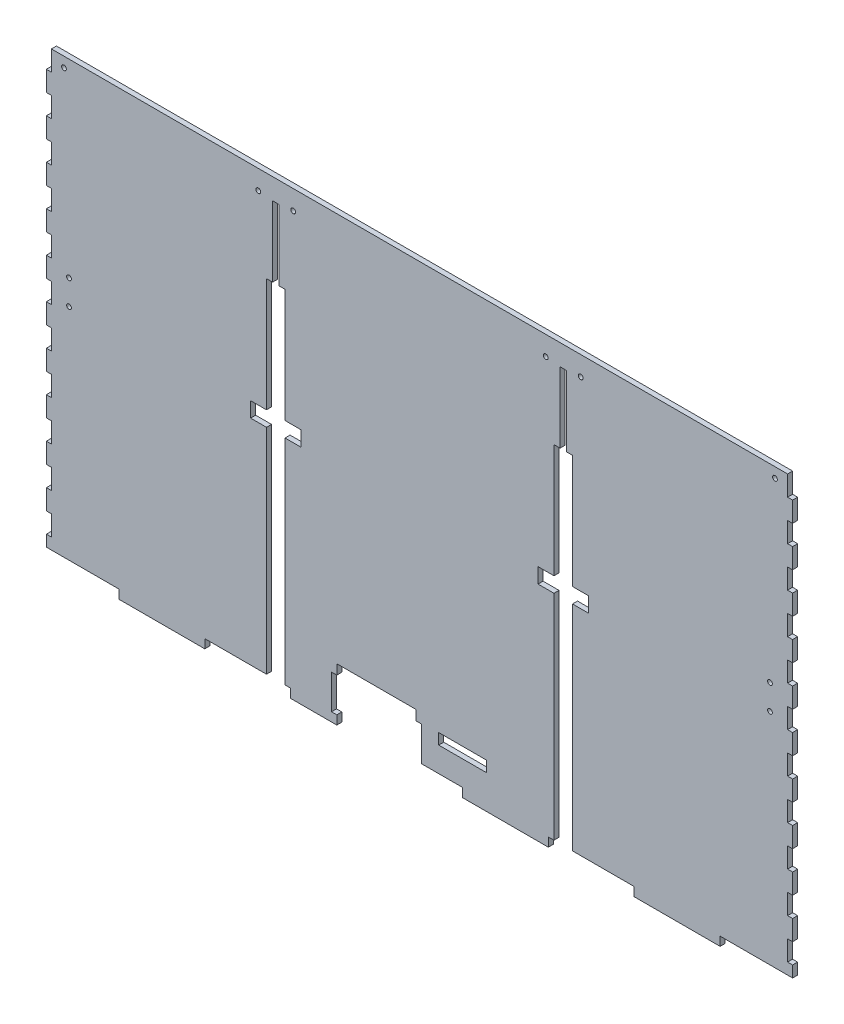
SolidWorks part; units mm, degrees
material "Acrylic (Medium-high impact)"
ref_plane "Front Plane" through (0, 0, 0) normal (0, 0, 1) x (1, 0, 0)
ref_plane "Top Plane" through (0, 0, 0) normal (0, 1, 0) x (1, 0, 0)
ref_plane "Right Plane" through (0, 0, 0) normal (1, 0, 0) x (0, 0, -1)
sketch "Sketch1" plane through (0, 0, 0) normal (0, 0, 1) x (1, 0, 0)
  line L0 (0, 139.7) -> (0, -139.7) construction
  line L1 (-406.4, 139.7) -> (406.4, 139.7)
  line L2 (-406.4, 139.7) -> (-406.4, -139.7)
  line L3 (-406.4, -139.7) -> (406.4, -139.7)
  line L4 (406.4, 139.7) -> (406.4, -139.7)
  line L49 (-381, 127) -> (-381, 114.3)
  line L54 (-381, 139.7) -> (-377.825, 139.7)
  line L55 (-381, 139.7) -> (-381, 127)
  line L56 (-381, 127) -> (-377.825, 127)
  line L57 (-377.825, 139.7) -> (-377.825, 127)
  line L58 (-381, 127) -> (-377.825, 127)
  line L59 (-377.825, 127) -> (-377.825, 114.3)
  line L60 (-381, 114.3) -> (-377.825, 114.3)
  line L61 (-381, 114.3) -> (-381, 101.6)
  line L62 (-381, 114.3) -> (-377.825, 114.3)
  line L63 (-377.825, 114.3) -> (-377.825, 101.6)
  line L64 (-381, 101.6) -> (-377.825, 101.6)
  line L65 (-381, 101.6) -> (-381, 88.9)
  line L66 (-381, 101.6) -> (-377.825, 101.6)
  line L67 (-377.825, 101.6) -> (-377.825, 88.9)
  line L68 (-381, 88.9) -> (-377.825, 88.9)
  line L69 (-381, 88.9) -> (-381, 76.2)
  line L70 (-381, 88.9) -> (-377.825, 88.9)
  line L71 (-377.825, 88.9) -> (-377.825, 76.2)
  line L72 (-381, 76.2) -> (-377.825, 76.2)
  line L73 (-381, 76.2) -> (-381, 63.5)
  line L74 (-381, 76.2) -> (-377.825, 76.2)
  line L75 (-377.825, 76.2) -> (-377.825, 63.5)
  line L76 (-381, 63.5) -> (-377.825, 63.5)
  line L77 (-381, 63.5) -> (-381, 50.8)
  line L78 (-381, 63.5) -> (-377.825, 63.5)
  line L79 (-377.825, 63.5) -> (-377.825, 50.8)
  line L80 (-381, 50.8) -> (-377.825, 50.8)
  line L81 (-381, 50.8) -> (-381, 38.1)
  line L82 (-381, 50.8) -> (-377.825, 50.8)
  line L83 (-377.825, 50.8) -> (-377.825, 38.1)
  line L84 (-381, 38.1) -> (-377.825, 38.1)
  line L85 (-381, 38.1) -> (-381, 25.4)
  line L86 (-381, 38.1) -> (-377.825, 38.1)
  line L87 (-377.825, 38.1) -> (-377.825, 25.4)
  line L88 (-381, 25.4) -> (-377.825, 25.4)
  line L89 (377.825, 127) -> (377.825, 114.3)
  line L90 (377.825, 139.7) -> (381, 139.7)
  line L91 (377.825, 139.7) -> (377.825, 127)
  line L92 (377.825, 127) -> (381, 127)
  line L93 (381, 139.7) -> (381, 127)
  line L94 (377.825, 127) -> (381, 127)
  line L95 (381, 127) -> (381, 114.3)
  line L96 (377.825, 114.3) -> (381, 114.3)
  line L97 (377.825, 114.3) -> (377.825, 101.6)
  line L98 (377.825, 114.3) -> (381, 114.3)
  line L99 (381, 114.3) -> (381, 101.6)
  line L100 (377.825, 101.6) -> (381, 101.6)
  line L101 (377.825, 101.6) -> (377.825, 88.9)
  line L102 (377.825, 101.6) -> (381, 101.6)
  line L103 (381, 101.6) -> (381, 88.9)
  line L104 (377.825, 88.9) -> (381, 88.9)
  line L105 (377.825, 88.9) -> (377.825, 76.2)
  line L106 (377.825, 88.9) -> (381, 88.9)
  line L107 (381, 88.9) -> (381, 76.2)
  line L108 (377.825, 76.2) -> (381, 76.2)
  line L109 (377.825, 76.2) -> (377.825, 63.5)
  line L110 (377.825, 76.2) -> (381, 76.2)
  line L111 (381, 76.2) -> (381, 63.5)
  line L112 (377.825, 63.5) -> (381, 63.5)
  line L113 (377.825, 63.5) -> (377.825, 50.8)
  line L114 (377.825, 63.5) -> (381, 63.5)
  line L115 (381, 63.5) -> (381, 50.8)
  line L116 (377.825, 50.8) -> (381, 50.8)
  line L117 (377.825, 50.8) -> (377.825, 38.1)
  line L118 (377.825, 50.8) -> (381, 50.8)
  line L119 (381, 50.8) -> (381, 38.1)
  line L120 (377.825, 38.1) -> (381, 38.1)
  line L121 (377.825, 38.1) -> (377.825, 25.4)
  line L122 (377.825, 38.1) -> (381, 38.1)
  line L123 (381, 38.1) -> (381, 25.4)
  line L124 (377.825, 25.4) -> (381, 25.4)
  line L125 (-352.2133, -134.112) -> (-352.2133, -139.7)
  line L126 (-406.4, -134.112) -> (-352.2133, -134.112)
  line L127 (-406.4, -134.112) -> (-406.4, -139.7)
  line L128 (-406.4, -139.7) -> (-352.2133, -139.7)
  line L129 (-352.2133, -134.112) -> (-352.2133, -139.7)
  line L130 (-352.2133, -134.112) -> (-298.0267, -134.112)
  line L131 (-298.0267, -134.112) -> (-298.0267, -139.7)
  line L132 (-352.2133, -139.7) -> (-298.0267, -139.7)
  line L133 (-298.0267, -134.112) -> (-298.0267, -139.7)
  line L134 (-298.0267, -134.112) -> (-243.84, -134.112)
  line L135 (-243.84, -134.112) -> (-243.84, -139.7)
  line L136 (-298.0267, -139.7) -> (-243.84, -139.7)
  line L137 (-243.84, -134.112) -> (-243.84, -139.7)
  line L138 (-243.84, -134.112) -> (-189.6533, -134.112)
  line L139 (-189.6533, -134.112) -> (-189.6533, -139.7)
  line L140 (-243.84, -139.7) -> (-189.6533, -139.7)
  line L141 (-189.6533, -134.112) -> (-189.6533, -139.7)
  line L142 (-189.6533, -134.112) -> (-135.4667, -134.112)
  line L143 (-135.4667, -134.112) -> (-135.4667, -139.7)
  line L144 (-189.6533, -139.7) -> (-135.4667, -139.7)
  line L145 (-135.4667, -134.112) -> (-135.4667, -139.7)
  line L146 (-135.4667, -134.112) -> (-81.28, -134.112)
  line L147 (-81.28, -134.112) -> (-81.28, -139.7)
  line L148 (-135.4667, -139.7) -> (-81.28, -139.7)
  line L149 (-81.28, -134.112) -> (-81.28, -139.7)
  line L150 (-81.28, -134.112) -> (-27.0933, -134.112)
  line L151 (-27.0933, -134.112) -> (-27.0933, -139.7)
  line L152 (-81.28, -139.7) -> (-27.0933, -139.7)
  line L153 (-27.0933, -134.112) -> (-27.0933, -139.7)
  line L154 (-27.0933, -134.112) -> (27.0933, -134.112)
  line L155 (27.0933, -134.112) -> (27.0933, -139.7)
  line L156 (-27.0933, -139.7) -> (27.0933, -139.7)
  line L157 (27.0933, -134.112) -> (27.0933, -139.7)
  line L158 (27.0933, -134.112) -> (81.28, -134.112)
  line L159 (81.28, -134.112) -> (81.28, -139.7)
  line L160 (27.0933, -139.7) -> (81.28, -139.7)
  line L161 (81.28, -134.112) -> (81.28, -139.7)
  line L162 (81.28, -134.112) -> (135.4667, -134.112)
  line L163 (135.4667, -134.112) -> (135.4667, -139.7)
  line L164 (81.28, -139.7) -> (135.4667, -139.7)
  line L165 (135.4667, -134.112) -> (135.4667, -139.7)
  line L166 (135.4667, -134.112) -> (189.6533, -134.112)
  line L167 (189.6533, -134.112) -> (189.6533, -139.7)
  line L168 (135.4667, -139.7) -> (189.6533, -139.7)
  line L169 (189.6533, -134.112) -> (189.6533, -139.7)
  line L170 (189.6533, -134.112) -> (243.84, -134.112)
  line L171 (243.84, -134.112) -> (243.84, -139.7)
  line L172 (189.6533, -139.7) -> (243.84, -139.7)
  line L173 (243.84, -134.112) -> (243.84, -139.7)
  line L174 (243.84, -134.112) -> (298.0267, -134.112)
  line L175 (298.0267, -134.112) -> (298.0267, -139.7)
  line L176 (243.84, -139.7) -> (298.0267, -139.7)
  line L177 (298.0267, -134.112) -> (298.0267, -139.7)
  line L178 (298.0267, -134.112) -> (352.2133, -134.112)
  line L179 (352.2133, -134.112) -> (352.2133, -139.7)
  line L180 (298.0267, -139.7) -> (352.2133, -139.7)
  line L181 (352.2133, -134.112) -> (352.2133, -139.7)
  line L182 (352.2133, -134.112) -> (406.4, -134.112)
  line L183 (406.4, -134.112) -> (406.4, -139.7)
  line L184 (352.2133, -139.7) -> (406.4, -139.7)
  line L205 (-90.678, 84.5227) -> (-90.678, -139.7) construction
  line L206 (90.678, 84.5227) -> (90.678, -139.7) construction
  line L207 (-90.678, -27.5886) -> (90.678, -27.5886) construction
  line L208 (-381, 25.4) -> (-381, 12.7)
  line L209 (-381, 25.4) -> (-377.825, 25.4)
  line L210 (-377.825, 25.4) -> (-377.825, 12.7)
  line L211 (-381, 12.7) -> (-377.825, 12.7)
  line L212 (-381, 12.7) -> (-381, 0)
  line L213 (-381, 12.7) -> (-377.825, 12.7)
  line L214 (-377.825, 12.7) -> (-377.825, 0)
  line L215 (-381, 0) -> (-377.825, 0)
  line L224 (-377.825, 0) -> (377.825, 0) construction
  line L229 (377.825, 25.4) -> (377.825, 12.7)
  line L230 (377.825, 25.4) -> (381, 25.4)
  line L231 (381, 25.4) -> (381, 12.7)
  line L232 (377.825, 12.7) -> (381, 12.7)
  line L233 (377.825, 12.7) -> (377.825, 0)
  line L234 (377.825, 12.7) -> (381, 12.7)
  line L235 (381, 12.7) -> (381, 0)
  line L236 (377.825, 0) -> (381, 0)
  line L237 (-381, 0) -> (-381, -12.7)
  line L238 (-381, 0) -> (-377.825, 0)
  line L239 (-377.825, 0) -> (-377.825, -12.7)
  line L240 (-381, -12.7) -> (-377.825, -12.7)
  line L241 (-381, -12.7) -> (-381, -25.4)
  line L242 (-381, -12.7) -> (-377.825, -12.7)
  line L243 (-377.825, -12.7) -> (-377.825, -25.4)
  line L244 (-381, -25.4) -> (-377.825, -25.4)
  line L245 (-381, -25.4) -> (-381, -38.1)
  line L246 (-381, -25.4) -> (-377.825, -25.4)
  line L247 (-377.825, -25.4) -> (-377.825, -38.1)
  line L248 (-381, -38.1) -> (-377.825, -38.1)
  line L249 (-381, -38.1) -> (-381, -50.8)
  line L250 (-381, -38.1) -> (-377.825, -38.1)
  line L251 (-377.825, -38.1) -> (-377.825, -50.8)
  line L252 (-381, -50.8) -> (-377.825, -50.8)
  line L253 (-381, -50.8) -> (-381, -63.5)
  line L254 (-381, -50.8) -> (-377.825, -50.8)
  line L255 (-377.825, -50.8) -> (-377.825, -63.5)
  line L256 (-381, -63.5) -> (-377.825, -63.5)
  line L257 (-381, -63.5) -> (-381, -76.2)
  line L258 (-381, -63.5) -> (-377.825, -63.5)
  line L259 (-377.825, -63.5) -> (-377.825, -76.2)
  line L260 (-381, -76.2) -> (-377.825, -76.2)
  line L261 (-381, -76.2) -> (-381, -88.9)
  line L262 (-381, -76.2) -> (-377.825, -76.2)
  line L263 (-377.825, -76.2) -> (-377.825, -88.9)
  line L264 (-381, -88.9) -> (-377.825, -88.9)
  line L265 (-381, -88.9) -> (-381, -101.6)
  line L266 (-381, -88.9) -> (-377.825, -88.9)
  line L267 (-377.825, -88.9) -> (-377.825, -101.6)
  line L268 (-381, -101.6) -> (-377.825, -101.6)
  line L269 (-381, -101.6) -> (-381, -114.3)
  line L270 (-381, -101.6) -> (-377.825, -101.6)
  line L271 (-377.825, -101.6) -> (-377.825, -114.3)
  line L272 (-381, -114.3) -> (-377.825, -114.3)
  line L273 (-381, -114.3) -> (-381, -127)
  line L274 (-381, -114.3) -> (-377.825, -114.3)
  line L275 (-377.825, -114.3) -> (-377.825, -127)
  line L276 (-381, -127) -> (-377.825, -127)
  line L277 (-381, -127) -> (-381, -139.7)
  line L278 (-381, -127) -> (-377.825, -127)
  line L279 (-377.825, -127) -> (-377.825, -139.7)
  line L280 (-381, -139.7) -> (-377.825, -139.7)
  line L281 (377.825, 0) -> (377.825, -12.7)
  line L282 (377.825, 0) -> (381, 0)
  line L283 (381, 0) -> (381, -12.7)
  line L284 (377.825, -12.7) -> (381, -12.7)
  line L285 (377.825, -12.7) -> (377.825, -25.4)
  line L286 (377.825, -12.7) -> (381, -12.7)
  line L287 (381, -12.7) -> (381, -25.4)
  line L288 (377.825, -25.4) -> (381, -25.4)
  line L289 (377.825, -25.4) -> (377.825, -38.1)
  line L290 (377.825, -25.4) -> (381, -25.4)
  line L291 (381, -25.4) -> (381, -38.1)
  line L292 (377.825, -38.1) -> (381, -38.1)
  line L293 (377.825, -38.1) -> (377.825, -50.8)
  line L294 (377.825, -38.1) -> (381, -38.1)
  line L295 (381, -38.1) -> (381, -50.8)
  line L296 (377.825, -50.8) -> (381, -50.8)
  line L297 (377.825, -50.8) -> (377.825, -63.5)
  line L298 (377.825, -50.8) -> (381, -50.8)
  line L299 (381, -50.8) -> (381, -63.5)
  line L300 (377.825, -63.5) -> (381, -63.5)
  line L301 (377.825, -63.5) -> (377.825, -76.2)
  line L302 (377.825, -63.5) -> (381, -63.5)
  line L303 (381, -63.5) -> (381, -76.2)
  line L304 (377.825, -76.2) -> (381, -76.2)
  line L305 (377.825, -76.2) -> (377.825, -88.9)
  line L306 (377.825, -76.2) -> (381, -76.2)
  line L307 (381, -76.2) -> (381, -88.9)
  line L308 (377.825, -88.9) -> (381, -88.9)
  line L309 (377.825, -88.9) -> (377.825, -101.6)
  line L310 (377.825, -88.9) -> (381, -88.9)
  line L311 (381, -88.9) -> (381, -101.6)
  line L312 (377.825, -101.6) -> (381, -101.6)
  line L313 (377.825, -101.6) -> (377.825, -114.3)
  line L314 (377.825, -101.6) -> (381, -101.6)
  line L315 (381, -101.6) -> (381, -114.3)
  line L316 (377.825, -114.3) -> (381, -114.3)
  line L317 (377.825, -114.3) -> (377.825, -127)
  line L318 (377.825, -114.3) -> (381, -114.3)
  line L319 (381, -114.3) -> (381, -127)
  line L320 (377.825, -127) -> (381, -127)
  line L321 (377.825, -127) -> (377.825, -139.7)
  line L322 (377.825, -127) -> (381, -127)
  line L323 (381, -127) -> (381, -139.7)
  line L324 (377.825, -139.7) -> (381, -139.7)
  point P6 (0, 0)
  point P128 (0, -27.5886)
  point P153 (0, 0)
  dimension "D4" = 12.7
  dimension "D5" = 3.175
  dimension "D10" = 181.356
  dimension "D12" = 755.65
  dimension "D8" = 812.8
  dimension "D11" = 54.1867
  dimension "D2" = 273.812
  dimension "D9" = 279.4
  dimension "D3" = 22
  dimension "D7" = 15
extrude "Main Extrude" add sketch "Sketch1" along normal blind 3.175 contours L321 L317 L313 L309 L305 L301 L297 L293 L289 L285 L281 L233 L229 L121 L117 L113 L109 L105 L101 L97 L89 L91 L1 L57 L59 L63 L67 L71 L75 L79 L83 L87 L210 L214 L239 L243 L247 L251 L255 L259 L263 L267 L271 L275 L279 L126 L130 L134 L138 L142 L146 | L277 L273 L269 L265 L261 L257 L253 L249 L245 L241 L237 L212 L208 L85 L81 L77 L73 L69 L65 L61 L49 L55 L1 L2 L126 | L319 L323 L182 L4 L1 L93 L95 L99 L103 L107 L111 L115 L119 L123 L231 L235 L283 L287 L291 L295 L299 L303 L307 L311 L315 | L126 L279 L3 L125 | L135 L134 L131 L3 | L143 L142 L139 L3 | L151 L150 L147 L3 | L159 L158 L155 L3 | L167 L166 L163 L3 | L175 L174 L171 L3 | L323 L182 L321 L184 | L89 L96 L95 L92 | L101 L104 L103 L100 | L109 L112 L111 L108 | L117 L120 L119 L116 | L229 L232 L231 L124 | L281 L284 L283 L236 | L289 L292 L291 L288 | L297 L300 L299 L296 | L305 L308 L307 L304 | L313 L316 L315 L312 | L323 L320 L321 L182 | L49 L60 L59 L56 | L65 L68 L67 L64 | L73 L76 L75 L72 | L81 L84 L83 L80 | L208 L211 L210 L88 | L237 L240 L239 L215 | L245 L248 L247 L244 | L253 L256 L255 L252 | L261 L264 L263 L260 | L269 L272 L271 L268 | L279 L276 L277 L126 | L277 L126 L2 L3 | L321 L182 L179 L3 | L182 L323 L3 L4 | L279 L126 L277 L128 region at (-393.7, 2.794, 0) region at (-393.7, -136.906, 0) region at (0, 2.794, 0) region at (-379.4125, 120.65, 0) region at (-379.4125, -130.556, 0) region at (-379.4125, -136.906, 0) region at (-365.0192, -136.906, 0) region at (393.7, 2.794, 0) region at (379.4125, 120.65, 0) region at (-379.4125, 95.25, 0) region at (-379.4125, -107.95, 0) region at (-270.9333, -136.906, 0) region at (393.7, -136.906, 0) region at (379.4125, 95.25, 0) region at (-379.4125, 69.85, 0) region at (-379.4125, -82.55, 0) region at (379.4125, -136.906, 0) region at (379.4125, -130.556, 0) region at (-162.56, -136.906, 0) region at (365.0192, -136.906, 0) region at (379.4125, 69.85, 0) region at (-379.4125, 44.45, 0) region at (-379.4125, -57.15, 0) region at (379.4125, -107.95, 0) region at (-54.1867, -136.906, 0) region at (270.9333, -136.906, 0) region at (379.4125, 44.45, 0) region at (-379.4125, 19.05, 0) region at (-379.4125, -31.75, 0) region at (379.4125, -82.55, 0) region at (54.1867, -136.906, 0) region at (162.56, -136.906, 0) region at (379.4125, 19.05, 0) region at (-379.4125, -6.35, 0) region at (379.4125, -57.15, 0) region at (379.4125, -6.35, 0) region at (379.4125, -31.75, 0)
sketch "Sketch8" plane through (0, 0, 3.175) normal (0, 0, 1) x (1, 0, 0)
  line L0 (-406.4, 139.7) -> (-406.4, -139.7) construction
  line L1 (-381, 28.2575) -> (-384.175, 28.2575)
  line L2 (-381, 28.2575) -> (-381, -3.6195)
  line L3 (-381, -3.6195) -> (-384.175, -3.6195)
  line L4 (-384.175, 28.2575) -> (-384.175, -3.6195)
  line L5 (-406.4, -139.7) -> (-352.2133, -139.7) construction
  line L6 (381, 28.2575) -> (384.175, 28.2575)
  line L7 (381, 28.2575) -> (381, -3.6195)
  line L8 (381, -3.6195) -> (384.175, -3.6195)
  line L9 (384.175, 28.2575) -> (384.175, -3.6195)
  line L11 (-381, 88.9) -> (-381, 76.2) construction
  line L12 (-352.2133, -134.112) -> (-298.0267, -134.112) construction
  line L13 (381, 88.9) -> (381, 76.2) construction
  line L14 (-393.7, -120.65) -> (393.7, -120.65) construction
  circle A0 centre (-393.7, -120.65) radius 1.5
  circle A1 centre (393.7, -120.65) radius 1.5
  point P6 (0, -120.65)
  point P16 (-384.175, 12.319)
  dimension "D5" = 3
  dimension "D1" = 31.877
  dimension "D2" = 3.175
  dimension "D3" = 146.431
  dimension "D4" = 19.05
  dimension "D6" = 12.7
extrude "Mount Holes" cut sketch "Sketch8" against normal through all
sketch "Sketch3" plane through (0, 0, 3.175) normal (0, 0, 1) x (1, 0, 0)
  line L0 (-135.4667, -134.112) -> (-81.28, -134.112) construction
  line L1 (-96.52, 126.492) -> (-84.836, 126.492)
  line L2 (-96.52, 126.492) -> (-96.52, -134.112)
  line L3 (-96.52, -134.112) -> (-84.836, -134.112)
  line L4 (-84.836, 126.492) -> (-84.836, -134.112)
  line L5 (81.28, -134.112) -> (135.4667, -134.112) construction
  line L6 (84.836, 126.492) -> (96.52, 126.492)
  line L7 (84.836, 126.492) -> (84.836, -134.112)
  line L8 (84.836, -134.112) -> (96.52, -134.112)
  line L9 (96.52, 126.492) -> (96.52, -134.112)
  line L10 (-84.836, -3.81) -> (84.836, -3.81) construction
  line L12 (-106.553, 10.3505) -> (-74.803, 10.3505)
  line L13 (-106.553, 10.3505) -> (-106.553, 0.8255)
  line L14 (-106.553, 0.8255) -> (-74.803, 0.8255)
  line L15 (-74.803, 10.3505) -> (-74.803, 0.8255)
  line L16 (74.803, 10.3505) -> (106.553, 10.3505)
  line L17 (74.803, 10.3505) -> (74.803, 0.8255)
  line L18 (74.803, 0.8255) -> (106.553, 0.8255)
  line L19 (106.553, 10.3505) -> (106.553, 0.8255)
  line L20 (-96.52, 126.492) -> (-92.6465, 126.492)
  line L21 (-96.52, 126.492) -> (-96.52, 82.042)
  line L22 (-96.52, 82.042) -> (-92.6465, 82.042)
  line L23 (-92.6465, 126.492) -> (-92.6465, 82.042)
  line L24 (-84.836, 126.492) -> (-88.7095, 126.492)
  line L25 (-84.836, 126.492) -> (-84.836, 82.042)
  line L26 (-84.836, 82.042) -> (-88.7095, 82.042)
  line L27 (-88.7095, 126.492) -> (-88.7095, 82.042)
  line L28 (84.836, 126.492) -> (88.7095, 126.492)
  line L29 (84.836, 126.492) -> (84.836, 82.042)
  line L30 (84.836, 82.042) -> (88.7095, 82.042)
  line L31 (88.7095, 126.492) -> (88.7095, 82.042)
  line L32 (96.52, 126.492) -> (92.6465, 126.492)
  line L33 (96.52, 126.492) -> (96.52, 82.042)
  line L34 (96.52, 82.042) -> (92.6465, 82.042)
  line L35 (92.6465, 126.492) -> (92.6465, 82.042)
  point P14 (-90.678, 126.492)
  point P15 (90.678, 126.492)
  point P16 (0, -3.81)
  point P27 (-90.678, 10.3505)
  point P28 (90.678, 10.3505)
  point P29 (-74.803, 5.588)
  dimension "D1" = 11.684
  dimension "D2" = 260.604
  dimension "D3" = 181.356
  dimension "D4" = 9.525
  dimension "D5" = 139.7
  dimension "D6" = 31.75
  dimension "D8" = 3.937
  dimension "D7" = 44.45
extrude "Door Slots" cut sketch "Sketch3" against normal through all contours L2 L12 L4 L1 | L2 L14 L4 L12 | L15 L12 L4 L14 | L13 L14 L2 L12 | L14 L2 L3 L4 | L7 L16 L9 L6 | L7 L18 L9 L16 | L19 L16 L9 L18 | L17 L18 L7 L16 | L18 L7 L8 L9 region at (-90.678, 56.2317, 3.175) region at (-90.678, 5.588, 3.175) region at (-101.5365, 5.588, 3.175) region at (-90.678, -66.6433, 3.175) region at (-79.8195, 5.588, 3.175) region at (90.678, 56.2317, 3.175) region at (90.678, 5.588, 3.175) region at (79.8195, 5.588, 3.175) region at (90.678, -66.6432, 3.175) region at (101.5365, 5.588, 3.175)
sketch "Sketch4" plane through (0, 0, 0) normal (0, 0, 1) x (1, 0, 0)
  line L1 (-81.28, -139.7) -> (-27.0933, -139.7) construction
  line L2 (-55.48, -112.41) -> (-52.178, -112.41)
  line L3 (-52.178, -112.41) -> (-52.178, -106.172)
  line L4 (-52.178, -106.172) -> (-2.178, -106.172)
  line L5 (-2.178, -106.172) -> (-2.178, -112.41)
  line L6 (-2.178, -112.41) -> (1.124, -112.41)
  line L9 (-55.48, -112.41) -> (-55.48, -134.112)
  line L10 (-55.48, -134.112) -> (-52.178, -134.112)
  line L11 (-52.178, -134.112) -> (-52.178, -139.7)
  line L12 (1.124, -112.41) -> (1.124, -134.112)
  line L13 (1.124, -134.112) -> (-2.178, -134.112)
  line L14 (-2.178, -134.112) -> (-2.178, -139.7)
  line L15 (-52.178, -139.7) -> (-2.178, -139.7)
  line L16 (-27.0933, -134.112) -> (27.0933, -134.112) construction
  line L18 (12.128, -111.633) -> (42.228, -111.633)
  line L19 (12.128, -111.633) -> (12.128, -118.491)
  line L20 (12.128, -118.491) -> (42.228, -118.491)
  line L21 (42.228, -111.633) -> (42.228, -118.491)
  line L22 (-27.0933, -134.112) -> (27.0933, -134.112) construction
  line L24 (-96.52, -134.112) -> (-84.836, -134.112) construction
  line L25 (84.836, -134.112) -> (96.52, -134.112) construction
  point P9 (-27.178, -106.172)
  point P10 (-27.178, -139.7)
  point P22 (27.178, -118.491)
  point P25 (90.678, -134.112)
  point P30 (-90.678, -134.112)
  dimension "D1" = 50
  dimension "D2" = 3.302
  dimension "D4" = 21.702
  dimension "D5" = 30.1
  dimension "D9" = 63.5
  dimension "D8" = 63.5
  dimension "D7" = 15.621
extrude "Trough and Lever Holes" cut sketch "Sketch4" along normal through all contours L11 L15 L14 L13 L12 L6 L5 L4 L3 L2 L9 L10 | L21 L18 L19 L20 region at (-27.178, -122.9616, 0) region at (27.178, -115.062, 0)
sketch "Sketch5" plane through (0, 0, 3.175) normal (0, 0, 1) x (1, 0, 0)
  line L0 (-90.678, 126.492) -> (-90.678, -134.112) construction
  line L1 (-96.52, 126.492) -> (-84.836, 126.492) construction
  line L2 (-96.52, -134.112) -> (-84.836, -134.112) construction
  line L3 (90.678, 126.492) -> (90.678, -134.112) construction
  line L4 (84.836, 126.492) -> (96.52, 126.492) construction
  line L5 (84.836, -134.112) -> (96.52, -134.112) construction
  line L6 (-135.4667, -134.112) -> (-96.52, -134.112) construction
  line L19 (-99.51, -134.112) -> (-95.8319, -134.112)
  line L20 (-99.51, -134.112) -> (-99.51, -108.712)
  line L21 (-99.51, -108.712) -> (-95.8319, -108.712)
  line L22 (-95.8319, -134.112) -> (-95.8319, -108.712)
  line L24 (-99.51, -108.712) -> (-95.8319, -108.712)
  line L25 (-99.51, -108.712) -> (-99.51, -83.312)
  line L26 (-99.51, -83.312) -> (-95.8319, -83.312)
  line L27 (-95.8319, -108.712) -> (-95.8319, -83.312)
  line L28 (-95.8319, -83.312) -> (-99.51, -83.312)
  line L29 (-95.8319, -83.312) -> (-95.8319, -57.912)
  line L30 (-95.8319, -57.912) -> (-99.51, -57.912)
  line L31 (-99.51, -83.312) -> (-99.51, -57.912)
  line L32 (-99.51, -57.912) -> (-95.8319, -57.912)
  line L33 (-99.51, -57.912) -> (-99.51, -32.512)
  line L34 (-99.51, -32.512) -> (-95.8319, -32.512)
  line L35 (-95.8319, -57.912) -> (-95.8319, -32.512)
  line L36 (-95.8319, -32.512) -> (-99.51, -32.512)
  line L37 (-95.8319, -32.512) -> (-95.8319, -7.112)
  line L38 (-95.8319, -7.112) -> (-99.51, -7.112)
  line L39 (-99.51, -32.512) -> (-99.51, -7.112)
  line L40 (-81.846, -108.712) -> (-85.5241, -108.712)
  line L41 (-85.5241, -134.112) -> (-85.5241, -108.712)
  line L42 (-81.846, -134.112) -> (-85.5241, -134.112)
  line L43 (-81.846, -134.112) -> (-81.846, -108.712)
  line L44 (-81.846, -83.312) -> (-85.5241, -83.312)
  line L45 (-85.5241, -108.712) -> (-85.5241, -83.312)
  line L46 (-81.846, -108.712) -> (-85.5241, -108.712)
  line L47 (-81.846, -108.712) -> (-81.846, -83.312)
  line L48 (-85.5241, -57.912) -> (-81.846, -57.912)
  line L49 (-81.846, -83.312) -> (-81.846, -57.912)
  line L50 (-85.5241, -83.312) -> (-81.846, -83.312)
  line L51 (-85.5241, -83.312) -> (-85.5241, -57.912)
  line L52 (-81.846, -32.512) -> (-85.5241, -32.512)
  line L53 (-85.5241, -57.912) -> (-85.5241, -32.512)
  line L54 (-81.846, -57.912) -> (-85.5241, -57.912)
  line L55 (-81.846, -57.912) -> (-81.846, -32.512)
  line L56 (-85.5241, -7.112) -> (-81.846, -7.112)
  line L57 (-81.846, -32.512) -> (-81.846, -7.112)
  line L58 (-85.5241, -32.512) -> (-81.846, -32.512)
  line L59 (-85.5241, -32.512) -> (-85.5241, -7.112)
  line L60 (0, -1.7463) -> (0, 1.7463) construction
  line L61 (99.51, -108.712) -> (95.8319, -108.712)
  line L62 (95.8319, -134.112) -> (95.8319, -108.712)
  line L63 (99.51, -134.112) -> (95.8319, -134.112)
  line L64 (99.51, -134.112) -> (99.51, -108.712)
  line L65 (99.51, -83.312) -> (95.8319, -83.312)
  line L66 (95.8319, -108.712) -> (95.8319, -83.312)
  line L67 (99.51, -108.712) -> (95.8319, -108.712)
  line L68 (99.51, -108.712) -> (99.51, -83.312)
  line L69 (95.8319, -57.912) -> (99.51, -57.912)
  line L70 (99.51, -83.312) -> (99.51, -57.912)
  line L71 (95.8319, -83.312) -> (99.51, -83.312)
  line L72 (95.8319, -83.312) -> (95.8319, -57.912)
  line L73 (99.51, -32.512) -> (95.8319, -32.512)
  line L74 (95.8319, -57.912) -> (95.8319, -32.512)
  line L75 (99.51, -57.912) -> (95.8319, -57.912)
  line L76 (99.51, -57.912) -> (99.51, -32.512)
  line L77 (95.8319, -7.112) -> (99.51, -7.112)
  line L78 (99.51, -32.512) -> (99.51, -7.112)
  line L79 (95.8319, -32.512) -> (99.51, -32.512)
  line L80 (95.8319, -32.512) -> (95.8319, -7.112)
  line L81 (85.5241, -32.512) -> (85.5241, -7.112)
  line L82 (85.5241, -32.512) -> (81.846, -32.512)
  line L83 (81.846, -32.512) -> (81.846, -7.112)
  line L84 (85.5241, -7.112) -> (81.846, -7.112)
  line L85 (81.846, -57.912) -> (81.846, -32.512)
  line L86 (81.846, -57.912) -> (85.5241, -57.912)
  line L87 (85.5241, -57.912) -> (85.5241, -32.512)
  line L88 (81.846, -32.512) -> (85.5241, -32.512)
  line L89 (85.5241, -83.312) -> (85.5241, -57.912)
  line L90 (85.5241, -83.312) -> (81.846, -83.312)
  line L91 (81.846, -83.312) -> (81.846, -57.912)
  line L92 (85.5241, -57.912) -> (81.846, -57.912)
  line L93 (81.846, -108.712) -> (81.846, -83.312)
  line L94 (81.846, -108.712) -> (85.5241, -108.712)
  line L95 (85.5241, -108.712) -> (85.5241, -83.312)
  line L96 (81.846, -83.312) -> (85.5241, -83.312)
  line L97 (81.846, -134.112) -> (81.846, -108.712)
  line L98 (81.846, -134.112) -> (85.5241, -134.112)
  line L99 (85.5241, -134.112) -> (85.5241, -108.712)
  line L100 (81.846, -108.712) -> (85.5241, -108.712)
  dimension "D1" = 25.4
  dimension "D3" = 5.1539
  dimension "D2" = 8.832
extrude "Door Guide Slots" [suppressed] cut sketch "Sketch5" against normal through all contours L21 L27 L26 L25 | L30 L35 L34 L33 | L48 L55 L52 L53 | L40 L47 L44 L45 | L86 L87 L82 L85 | L94 L95 L90 L93 | L69 L76 L73 L74 | L61 L68 L65 L66
sketch "Sketch7" plane through (0, 0, 3.175) normal (0, 0, 1) x (1, 0, 0)
  line L0 (-25.908, -109.9715) -> (25.908, -109.9715) construction
  line L1 (-56.008, -105.601) -> (-25.908, -105.601)
  line L2 (-56.008, -105.601) -> (-56.008, -114.342)
  line L3 (-56.008, -114.342) -> (-25.908, -114.342)
  line L4 (-25.908, -105.601) -> (-25.908, -114.342)
  line L5 (56.008, -105.601) -> (25.908, -105.601)
  line L6 (56.008, -105.601) -> (56.008, -114.342)
  line L7 (56.008, -114.342) -> (25.908, -114.342)
  line L8 (25.908, -105.601) -> (25.908, -114.342)
  line L9 (0, -109.9715) -> (0, 0) construction
  line L10 (-135.4667, -134.112) -> (-96.52, -134.112) construction
  line L11 (1.124, -134.112) -> (27.0933, -134.112) construction
  dimension "D1" = 28.511
  dimension "D2" = 30.1
  dimension "D3" = 51.816
  dimension "D4" = 19.77
extrude "Lever Holes" [suppressed] cut sketch "Sketch7" against normal through all
sketch "Sketch10" plane through (0, 0, 3.175) normal (0, 0, 1) x (1, 0, 0)
  line L0 (-101.678, 127.492) -> (-79.678, 127.492) construction
  line L2 (-92.6465, 126.492) -> (-88.7095, 126.492) construction
  line L3 (-90.678, 127.492) -> (-90.678, 126.492) construction
  line L4 (79.678, 127.492) -> (101.678, 127.492) construction
  line L5 (90.678, 127.492) -> (90.678, 126.492) construction
  line L6 (88.7095, 126.492) -> (92.6465, 126.492) construction
  circle A0 centre (-101.678, 127.492) radius 1.5
  circle A1 centre (-79.678, 127.492) radius 1.5
  circle A2 centre (79.678, 127.492) radius 1.5
  circle A3 centre (101.678, 127.492) radius 1.5
  dimension "D1" = 3
  dimension "D2" = 22
  dimension "D3" = 1
extrude "Door Guide Mount Holes" cut sketch "Sketch10" against normal through all
sketch "Sketch12" plane through (0, 0, 3.175) normal (0, 0, 1) x (1, 0, 0)
  line L0 (-246.507, 20.193) -> (-246.507, 4.445) construction
  line L1 (-221.107, 20.193) -> (-221.107, 4.445) construction
  line L2 (-246.507, 20.193) -> (-221.107, 20.193) construction
  line L3 (-246.507, 4.445) -> (-221.107, 4.445) construction
  line L4 (-243.332, 133.35) -> (-224.282, 133.35) construction
  line L5 (-406.4, 139.7) -> (406.4, 139.7) construction
  line L6 (-233.807, 20.193) -> (-233.807, 133.35) construction
  line L7 (-243.84, -134.112) -> (-189.6533, -134.112) construction
  line L8 (0, -1.7463) -> (0, 1.7463) construction
  line L9 (233.807, 20.193) -> (233.807, 133.35) construction
  line L10 (243.332, 133.35) -> (224.282, 133.35) construction
  line L11 (246.507, 4.445) -> (221.107, 4.445) construction
  line L12 (246.507, 20.193) -> (221.107, 20.193) construction
  line L13 (221.107, 20.193) -> (221.107, 4.445) construction
  line L14 (246.507, 20.193) -> (246.507, 4.445) construction
  circle A0 centre (-246.507, 20.193) radius 1.5
  circle A1 centre (-246.507, 4.445) radius 1.5
  circle A2 centre (-221.107, 4.445) radius 1.5
  circle A3 centre (-221.107, 20.193) radius 1.5
  circle A4 centre (-243.332, 133.35) radius 1.5
  circle A5 centre (-224.282, 133.35) radius 1.5
  circle A6 centre (224.282, 133.35) radius 1.5
  circle A7 centre (243.332, 133.35) radius 1.5
  circle A8 centre (221.107, 20.193) radius 1.5
  circle A9 centre (221.107, 4.445) radius 1.5
  circle A10 centre (246.507, 4.445) radius 1.5
  circle A11 centre (246.507, 20.193) radius 1.5
  point P12 (-233.807, 133.35)
  dimension "D1" = 3
  dimension "D2" = 233.807
  dimension "D3" = 19.05
  dimension "D4" = 6.35
  dimension "D5" = 25.4
  dimension "D6" = 15.748
  dimension "D7" = 138.557
extrude "Extension Clip Holes" cut sketch "Sketch12" against normal through all
sketch "Sketch11" plane through (0, 0, 3.175) normal (0, 0, 1) x (1, 0, 0)
  line L0 (-232.2195, 139.7) -> (-232.2195, 127)
  line L1 (-232.2195, 127) -> (-235.3945, 127)
  line L2 (-235.3945, 127) -> (-235.3945, 114.3)
  line L3 (-235.3945, 114.3) -> (-232.2195, 114.3)
  line L4 (232.2195, 139.7) -> (232.2195, 127)
  line L5 (232.2195, 127) -> (235.3945, 127)
  line L6 (235.3945, 127) -> (235.3945, 114.3)
  line L7 (235.3945, 114.3) -> (232.2195, 114.3)
  line L9 (-381, 127) -> (-377.825, 127) construction
  line L10 (-377.825, 139.7) -> (-377.825, 127) construction
  line L11 (235.3945, 120.65) -> (-235.3945, 120.65) construction
  line L12 (-232.2195, 114.3) -> (-232.2195, 101.6)
  line L13 (-232.2195, 101.6) -> (-235.3945, 101.6)
  line L14 (-235.3945, 101.6) -> (-235.3945, 88.9)
  line L15 (-235.3945, 88.9) -> (-232.2195, 88.9)
  line L16 (232.2195, 114.3) -> (232.2195, 101.6)
  line L17 (232.2195, 101.6) -> (235.3945, 101.6)
  line L18 (235.3945, 101.6) -> (235.3945, 88.9)
  line L19 (235.3945, 88.9) -> (232.2195, 88.9)
  line L20 (-232.2195, 88.9) -> (-232.2195, 76.2)
  line L21 (-232.2195, 76.2) -> (-235.3945, 76.2)
  line L22 (-235.3945, 76.2) -> (-235.3945, 63.5)
  line L23 (-235.3945, 63.5) -> (-232.2195, 63.5)
  line L24 (232.2195, 88.9) -> (232.2195, 76.2)
  line L25 (232.2195, 76.2) -> (235.3945, 76.2)
  line L26 (235.3945, 76.2) -> (235.3945, 63.5)
  line L27 (235.3945, 63.5) -> (232.2195, 63.5)
  line L28 (-232.2195, 63.5) -> (-232.2195, 50.8)
  line L29 (-232.2195, 50.8) -> (-235.3945, 50.8)
  line L30 (-235.3945, 50.8) -> (-235.3945, 38.1)
  line L31 (-235.3945, 38.1) -> (-232.2195, 38.1)
  line L32 (232.2195, 63.5) -> (232.2195, 50.8)
  line L33 (232.2195, 50.8) -> (235.3945, 50.8)
  line L34 (235.3945, 50.8) -> (235.3945, 38.1)
  line L35 (235.3945, 38.1) -> (232.2195, 38.1)
  line L36 (-232.2195, 38.1) -> (-232.2195, 25.4)
  line L37 (-232.2195, 25.4) -> (-235.3945, 25.4)
  line L38 (-235.3945, 25.4) -> (-235.3945, 12.7)
  line L39 (-235.3945, 12.7) -> (-232.2195, 12.7)
  line L40 (232.2195, 38.1) -> (232.2195, 25.4)
  line L41 (232.2195, 25.4) -> (235.3945, 25.4)
  line L42 (235.3945, 25.4) -> (235.3945, 12.7)
  line L43 (235.3945, 12.7) -> (232.2195, 12.7)
  line L44 (-232.2195, 12.7) -> (-232.2195, 0)
  line L45 (-232.2195, 0) -> (-235.3945, 0)
  line L46 (-235.3945, 0) -> (-235.3945, -12.7)
  line L47 (-235.3945, -12.7) -> (-232.2195, -12.7)
  line L48 (232.2195, 12.7) -> (232.2195, 0)
  line L50 (232.2195, 0) -> (235.3945, 0)
  line L52 (235.3945, 0) -> (235.3945, -12.7)
  line L53 (235.3945, -12.7) -> (232.2195, -12.7)
  line L54 (-232.2195, -12.7) -> (-232.2195, -25.4)
  line L55 (-232.2195, -25.4) -> (-235.3945, -25.4)
  line L56 (-235.3945, -25.4) -> (-235.3945, -38.1)
  line L57 (-235.3945, -38.1) -> (-232.2195, -38.1)
  line L58 (232.2195, -12.7) -> (232.2195, -25.4)
  line L59 (232.2195, -25.4) -> (235.3945, -25.4)
  line L60 (235.3945, -25.4) -> (235.3945, -38.1)
  line L61 (235.3945, -38.1) -> (232.2195, -38.1)
  line L62 (-232.2195, -38.1) -> (-232.2195, -50.8)
  line L63 (-232.2195, -50.8) -> (-235.3945, -50.8)
  line L64 (-235.3945, -50.8) -> (-235.3945, -63.5)
  line L65 (-235.3945, -63.5) -> (-232.2195, -63.5)
  line L66 (232.2195, -38.1) -> (232.2195, -50.8)
  line L67 (232.2195, -50.8) -> (235.3945, -50.8)
  line L68 (235.3945, -50.8) -> (235.3945, -63.5)
  line L69 (235.3945, -63.5) -> (232.2195, -63.5)
  line L70 (-232.2195, -63.5) -> (-232.2195, -76.2)
  line L71 (-232.2195, -76.2) -> (-235.3945, -76.2)
  line L72 (-235.3945, -76.2) -> (-235.3945, -88.9)
  line L73 (-235.3945, -88.9) -> (-232.2195, -88.9)
  line L74 (232.2195, -63.5) -> (232.2195, -76.2)
  line L75 (232.2195, -76.2) -> (235.3945, -76.2)
  line L76 (235.3945, -76.2) -> (235.3945, -88.9)
  line L77 (235.3945, -88.9) -> (232.2195, -88.9)
  line L78 (-232.2195, -88.9) -> (-232.2195, -101.6)
  line L79 (-232.2195, -101.6) -> (-235.3945, -101.6)
  line L80 (-235.3945, -101.6) -> (-235.3945, -114.3)
  line L81 (-235.3945, -114.3) -> (-232.2195, -114.3)
  line L82 (232.2195, -88.9) -> (232.2195, -101.6)
  line L83 (232.2195, -101.6) -> (235.3945, -101.6)
  line L84 (235.3945, -101.6) -> (235.3945, -114.3)
  line L85 (235.3945, -114.3) -> (232.2195, -114.3)
  line L86 (-232.2195, -114.3) -> (-232.2195, -127)
  line L87 (-232.2195, -127) -> (-235.3945, -127)
  line L88 (-235.3945, -127) -> (-235.3945, -139.7)
  line L90 (232.2195, -114.3) -> (232.2195, -127)
  line L91 (232.2195, -127) -> (235.3945, -127)
  line L92 (235.3945, -127) -> (235.3945, -139.7)
  line L98 (-406.4, 139.7) -> (406.4, 139.7)
  line L99 (-406.4, 139.7) -> (-406.4, -139.7)
  line L100 (-406.4, -139.7) -> (406.4, -139.7)
  line L101 (406.4, 139.7) -> (406.4, -139.7)
  line L102 (-235.3945, -139.7) -> (-232.2195, -139.7)
  line L103 (235.3945, -139.7) -> (232.2195, -139.7)
  point P14 (-233.807, 127)
  point P15 (233.807, 114.3)
  point P18 (0, 120.65)
  dimension "D2" = 11
  dimension "D1" = 467.614
extrude "Extended Side Cut" [suppressed] cut sketch "Sketch11" against normal through all
extrude "Extension Center Cut" cut sketch "Sketch11<3>" against normal through all contours L99 L100 L39 L31 L23 L15 L2 L1 L98 | L101 L98 L80 L77 L76 L75 L72 L69 L68 L67 L64 L61 L60 L59 L56 L53 L52 L50 L100 region at (-320.0962, 0.0584, 3.175) region at (320.0962, 0.0584, 3.175)
sketch "Sketch11<3>" plane through (0, 0, 3.175) normal (0, 0, 1) x (1, 0, 0) same geometry as "Sketch11"
sketch "Sketch14" plane through (0, 0, 3.175) normal (0, 0, 1) x (1, 0, 0)
  line L1 (-232.2195, 139.7) -> (232.2195, 139.7)
  line L2 (-232.2195, 139.7) -> (-232.2195, 165.1)
  line L3 (-232.2195, 165.1) -> (232.2195, 165.1)
  line L4 (232.2195, 139.7) -> (232.2195, 165.1)
  dimension "D1" = 25.4
extrude "Extra Inch" [suppressed] add sketch "Sketch14" against normal up to surface (3.175 mm away)
sketch "Sketch15" [suppressed] plane through (0, 0, 3.175) normal (0, 0, 1) x (1, 0, 0)
  line L1 (-232.2195, 139.7) -> (232.2195, 139.7)
  line L2 (-232.2195, 139.7) -> (-232.2195, 165.1)
  line L3 (-232.2195, 165.1) -> (232.2195, 165.1)
  line L4 (232.2195, 139.7) -> (232.2195, 165.1)
  dimension "D1" = 25.4
extrude "Back Extra Inch" [suppressed] add sketch "Sketch15" against normal up to surface (3.175 mm away)
sketch "Sketch16" [suppressed] plane through (0, 0, 3.175) normal (0, 0, 1) x (1, 0, 0)
  line L1 (-232.2195, 139.7) -> (-406.4, 139.7)
  line L2 (-232.2195, 139.7) -> (-232.2195, 165.1)
  line L3 (-232.2195, 165.1) -> (-406.4, 165.1)
  line L4 (-406.4, 139.7) -> (-406.4, 165.1)
  dimension "D1" = 25.4
extrude "Extended Extra Inch" [suppressed] add sketch "Sketch16" against normal up to surface (3.175 mm away)
equation "\"bottomThickness\"= .220in"
equation "\"wallThickness\"= .125in"
equation "\"D4@Sketch1\"=\"D9@Sketch1\"/\"D3@Sketch1\""
equation "\"D5@Sketch1\"=\"wallThickness\""
equation "\"D1@Main Extrude\" = \"wallThickness\""
equation "\"D1@Sketch3\"=\"wallThickness\"*2+.19in+.02in"
equation "\"D2@Sketch4\"=\"wallThickness\"+.005in"
equation "\"D11@Sketch1\"=\"D8@Sketch1\"/\"D7@Sketch1\""
equation "\"D9@Sketch1\"=\"D2@Sketch1\"+\"bottomThickness\""
equation "\"D3@Sketch5\"=(\"wallThickness\"*2+.19in+.04)/2-(\"wallThickness\"-\"wallThickness\"/tan(80))*cos(80)"
equation "\"D8@Sketch3\"=\"wallThickness\"+.03in"
equation "\"D4@Sketch4\"=\"wallThickness\"+18.4mm+.005in"
equation "\"D2@Sketch5\"=(\"wallThickness\"*2+.19in+.04)/2+\"wallThickness\"/sin(80)"
